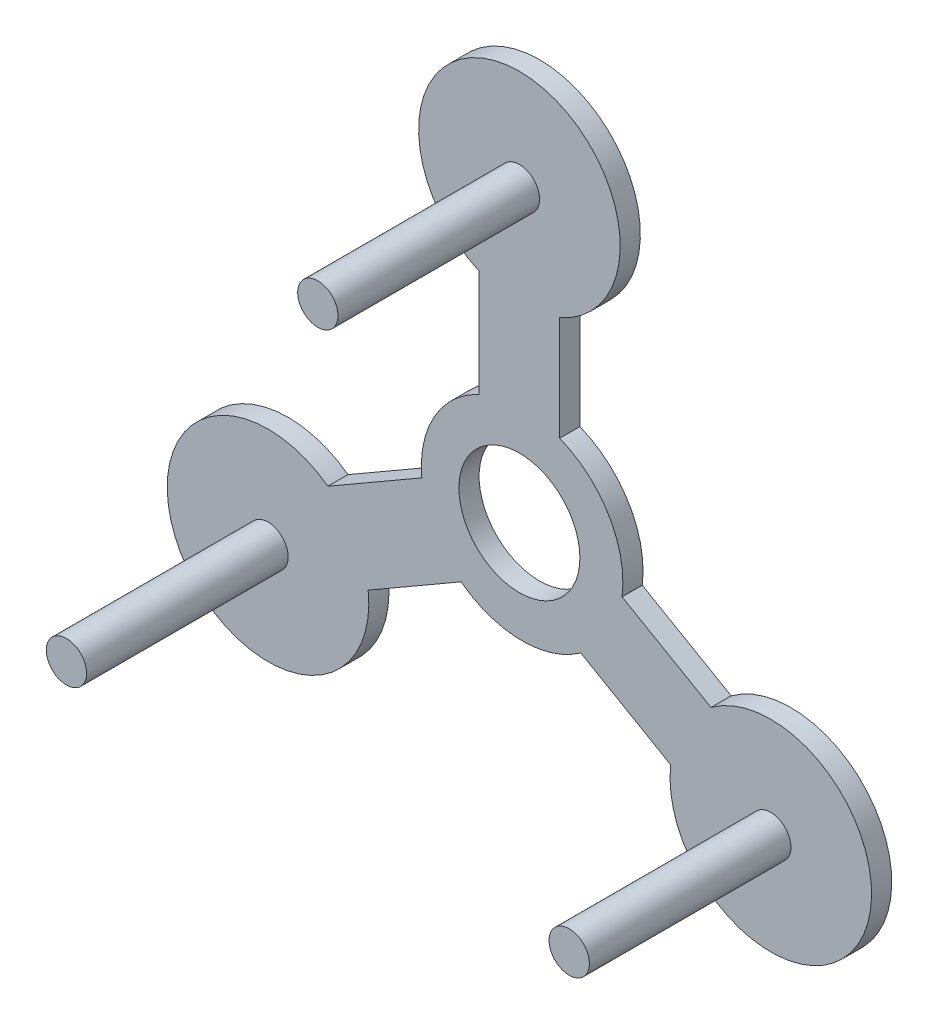
SolidWorks part; units mm, degrees
ref_plane "Front Plane" through (0, 0, 0) normal (0, 0, 1) x (1, 0, 0)
ref_plane "Top Plane" through (0, 0, 0) normal (0, 1, 0) x (1, 0, 0)
ref_plane "Right Plane" through (0, 0, 0) normal (1, 0, 0) x (0, 0, -1)
sketch "Sketch1" plane through (0, 0, 0) normal (0, 0, 1) x (1, 0, 0)
  line L0 (0, 0) -> (0, 144) construction
  line L1 (20, 144) -> (-20, 144)
  line L6 (0, 0) -> (124.7077, -72) construction
  line L7 (0, 0) -> (-124.7077, -72) construction
  line L8 (114.7077, -89.3205) -> (134.7077, -54.6795)
  line L9 (-114.7077, -89.3205) -> (-134.7077, -54.6795)
  line L10 (-134.7077, -54.6795) -> (-20, 11.547)
  line L11 (-20, 11.547) -> (-20, 144)
  line L12 (20, 144) -> (20, 11.547)
  line L13 (20, 11.547) -> (134.7077, -54.6795)
  line L14 (114.7077, -89.3205) -> (0, -23.094)
  line L15 (0, -23.094) -> (-114.7077, -89.3205)
  point P6 (0, 144)
  point P10 (0, 0)
  point P12 (124.7077, -72)
  point P15 (-124.7077, -72)
  dimension "D1" = 3
extrude "Boss-Extrude2" add sketch "Sketch1" along normal blind 10
sketch "Sketch3" plane through (0, 0, 10) normal (0, 0, 1) x (1, 0, 0)
  line L0 (-134.7077, -54.6795) -> (-114.7077, -89.3205) construction
  circle A0 centre (-124.7077, -72) radius 50
  circle A1 centre (0, 144) radius 50
  circle A2 centre (124.7077, -72) radius 50
  point P11 (0, 0)
  dimension "D1" = 3
extrude "Boss-Extrude3" add sketch "Sketch3" against normal blind 10
sketch "Sketch4" plane through (0, 0, 10) normal (0, 0, 1) x (1, 0, 0)
  circle A1 centre (0, 144) radius 10
  circle A2 centre (124.7077, -72) radius 10
  circle A3 centre (-124.7077, -72) radius 10
  point P9 (0, 0)
  dimension "D1" = 3
extrude "Boss-Extrude4" add sketch "Sketch4" along normal blind 90
sketch "Sketch5" plane through (0, 0, 100) normal (0, 0, 1) x (1, 0, 0)
  circle A0 centre (0, 144) radius 10
extrude "Cut-Extrude1" cut sketch "Sketch5" against normal blind 30
sketch "Sketch6" plane through (0, 0, 10) normal (0, 0, 1) x (1, 0, 0)
  circle A0 centre (0, 0) radius 13
extrude "Cut-Extrude2" cut sketch "Sketch6" against normal blind 10
sketch "Sketch7" plane through (0, 0, 70) normal (0, 0, 1) x (1, 0, 0)
  circle A0 centre (0, 144) radius 10
extrude "Boss-Extrude5" add sketch "Sketch7" along normal blind 30
sketch "Sketch9" plane through (0, 0, 100) normal (0, 0, 1) x (1, 0, 0)
  circle A0 centre (0, 144) radius 10
extrude "Boss-Extrude6" add sketch "Sketch9" along normal blind 10
sketch "Sketch10" plane through (0, 0, 100) normal (0, 0, 1) x (1, 0, 0)
  circle A0 centre (-124.7077, -72) radius 10
extrude "Boss-Extrude7" add sketch "Sketch10" along normal blind 10
sketch "Sketch11" plane through (0, 0, 100) normal (0, 0, 1) x (1, 0, 0)
  circle A0 centre (124.7077, -72) radius 10
extrude "Boss-Extrude8" add sketch "Sketch11" along normal blind 10
sketch "Sketch12" plane through (0, 0, 10) normal (0, 0, 1) x (1, 0, 0)
  circle A0 centre (1.3308, 0) radius 50
extrude "Boss-Extrude9" add sketch "Sketch12" against normal blind 10
sketch "Sketch13" plane through (0, 0, 10) normal (0, 0, 1) x (1, 0, 0)
  circle A0 centre (0, 0) radius 30
extrude "Cut-Extrude3" cut sketch "Sketch13" against normal blind 10
